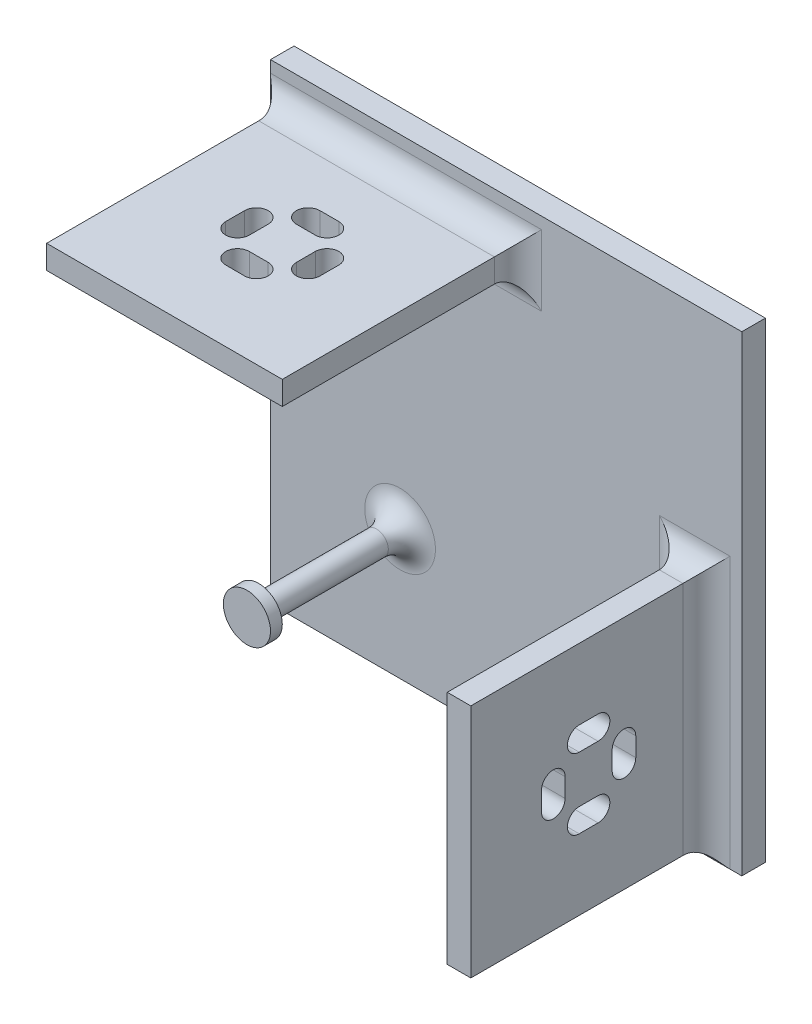
SolidWorks part; units mm, degrees
ref_plane "Front Plane" through (0, 0, 0) normal (0, 0, 1) x (1, 0, 0)
ref_plane "Top Plane" through (0, 0, 0) normal (0, 1, 0) x (1, 0, 0)
ref_plane "Right Plane" through (0, 0, 0) normal (1, 0, 0) x (0, 0, -1)
sketch "Sketch1" plane through (0, 0, 0) normal (0, 0, 1) x (1, 0, 0)
  line L1 (-25.4, -25.4) -> (25.4, -25.4)
  line L2 (-25.4, -25.4) -> (-25.4, 25.4)
  line L3 (-25.4, 25.4) -> (25.4, 25.4)
  line L4 (25.4, -25.4) -> (25.4, 25.4)
  line L5 (-25.4, -25.4) -> (25.4, 25.4) construction
  line L6 (-25.4, 25.4) -> (25.4, -25.4) construction
  point P0 (0, 0)
  dimension "D1" = 50.8
  dimension "D2" = 50.8
extrude "base" add sketch "Sketch1" along normal blind 2.54
sketch "Sketch2" plane through (0, 0, 2.54) normal (0, 0, 1) x (1, 0, 0)
  circle A0 centre (-11.43, -11.43) radius 1.27
  dimension "D1" = 2.54
extrude "post for wing" add sketch "Sketch2" along normal blind 15.24
sketch "Sketch4" plane through (0, 0, 2.54) normal (0, 0, 1) x (1, 0, 0)
  line L1 (-24.13, 19.05) -> (1.27, 19.05)
  line L2 (-24.13, 19.05) -> (-24.13, 21.59)
  line L3 (-24.13, 21.59) -> (1.27, 21.59)
  line L4 (1.27, 19.05) -> (1.27, 21.59)
  line L5 (-24.13, 19.05) -> (1.27, 21.59) construction
  line L6 (-24.13, 21.59) -> (1.27, 19.05) construction
  point P0 (-11.43, 20.32)
  dimension "D1" = 2.54
  dimension "D2" = 25.4
extrude "button holder" add sketch "Sketch4" along normal blind 25.4
ref_point "centre of button"
ref_axis "button axis" through (-11.43, 21.59, 15.24) along (0, 1, 0)
sketch "Sketch6" plane through (0, 21.59, 0) normal (0, 1, 0) x (1, 0, 0)
  line L0 (-12.446, -19.05) -> (-10.414, -19.05) construction
  line L1 (-12.446, -17.78) -> (-10.414, -17.78)
  line L2 (-12.446, -20.32) -> (-10.414, -20.32)
  arc A0 (-12.446, -17.78) -> (-12.446, -20.32) centre (-12.446, -19.05) ccw
  arc A1 (-10.414, -20.32) -> (-10.414, -17.78) centre (-10.414, -19.05) ccw
  point P2 (-11.43, -19.05)
  dimension "D2" = 1.27
  dimension "D1" = 2.032
  dimension "D3" = 0
  dimension "D4" = 3.81
extrude "one button leg hole" cut sketch "Sketch6" against normal blind 6.35
pattern_circular "moar leg holes" count 4 over 360 about axis through (-11.43, 21.59, 15.24) along (0, 1, 0) of "one button leg hole"
fillet "make everything not break" radius 2.54 4 edges at (1.27, 20.32, 2.54) (-11.43, 19.05, 2.54) (-11.43, 21.59, 2.54) (-24.13, 20.32, 2.54)
ref_axis "rotate for second button" through (-11.43, -11.43, 17.78) along (0, 0, -1)
pattern_circular "second button" count 2 every 90 about axis through (-11.43, -11.43, 17.78) along (0, 0, -1) of "button holder", "one button leg hole", "moar leg holes", "make everything not break"
sketch "Sketch3" plane through (0, 0, 17.78) normal (0, 0, 1) x (1, 0, 0)
  circle A0 centre (-11.43, -11.43) radius 2.54
  dimension "D1" = 5.08
extrude "don't let it fall off" add sketch "Sketch3" along normal blind 1.27
fillet "Fillet1" radius 2.54 1 edges at (-12.7, -11.43, 2.54)
